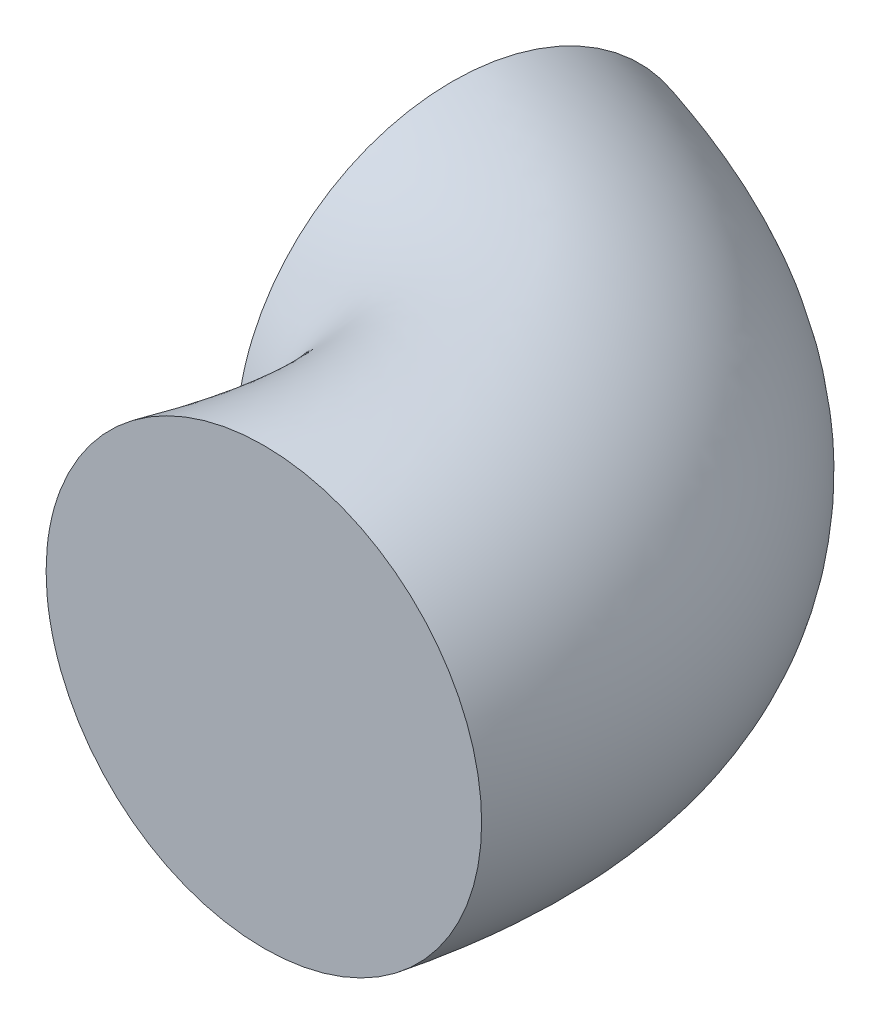
SolidWorks part; units mm, degrees
ref_plane "Front Plane" through (0, 0, 0) normal (0, 0, 1) x (1, 0, 0)
ref_plane "Top Plane" through (0, 0, 0) normal (0, 1, 0) x (1, 0, 0)
ref_plane "Right Plane" through (0, 0, 0) normal (1, 0, 0) x (0, 0, -1)
sketch "Sketch1" plane through (0, 0, 0) normal (0, 0, 1) x (1, 0, 0)
  circle A0 centre (0, 0) radius 40
sketch "Sketch2" plane through (0, 0, 0) normal (0, 1, 0) x (1, 0, 0)
  spline S0 degree 2 poles (0, 0) (16.6424, 56.3021) (-40.4409, 78.8312) knots 0 0 0 1 1 1
sweep "Sweep1" add profiles "Sketch1" path "Sketch2"
